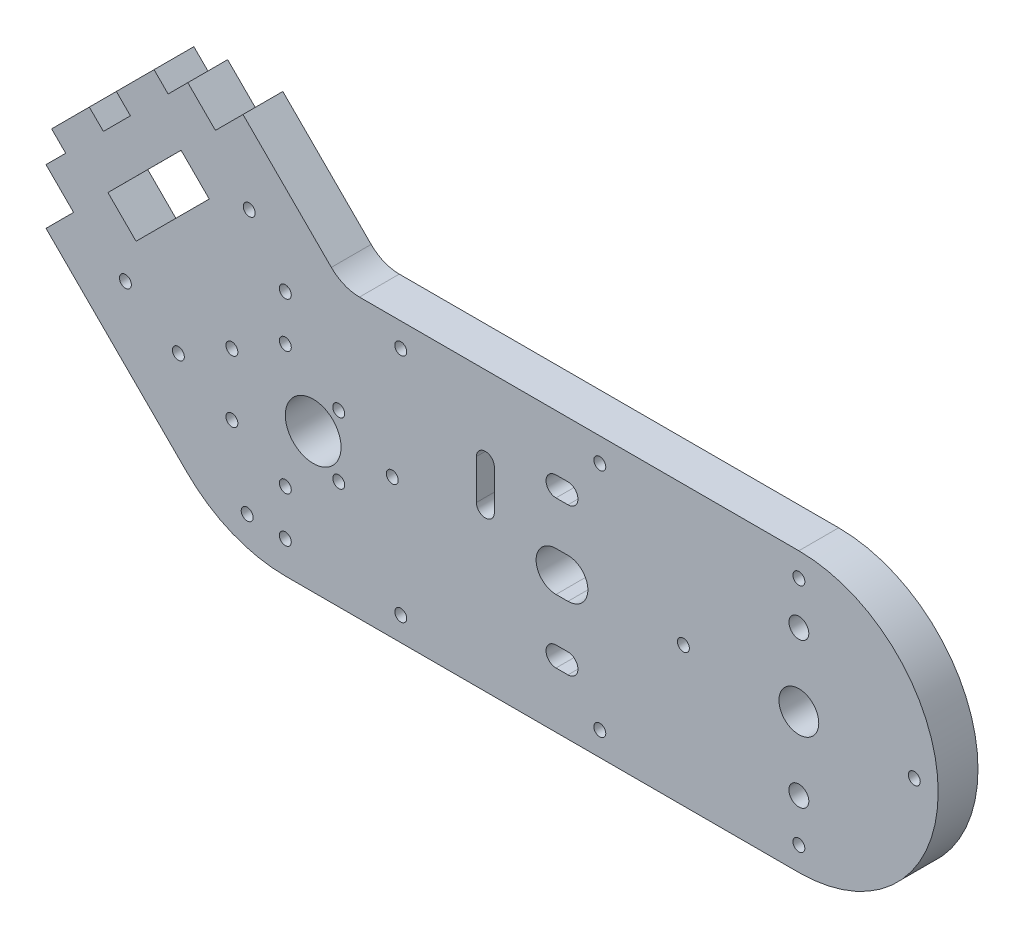
SolidWorks part; units mm, degrees
ref_plane "Front Plane" through (0, 0, 0) normal (0, 0, 1) x (1, 0, 0)
ref_plane "Top Plane" through (0, 0, 0) normal (0, 1, 0) x (1, 0, 0)
ref_plane "Right Plane" through (0, 0, 0) normal (1, 0, 0) x (0, 0, -1)
sketch "Sketch1" plane through (0, 0, 0) normal (0, 0, 1) x (1, 0, 0)
  line L0 (0, -35) -> (-129, -35)
  line L4 (0, 35) -> (-110.37, 35)
  line L9 (-58, 0) -> (-61, 0) construction
  line L10 (-58, -5) -> (-61, -5)
  line L11 (-58, 5) -> (-61, 5)
  line L13 (-58, 18.5) -> (-61, 18.5) construction
  line L14 (-58, 16) -> (-61, 16)
  line L15 (-58, 21) -> (-61, 21)
  line L17 (-58, -18.5) -> (-61, -18.5) construction
  line L18 (-58, -21) -> (-61, -21)
  line L19 (-58, -16) -> (-61, -16)
  line L20 (-78.75, 5) -> (-78.75, 15) construction
  line L21 (-81, 5) -> (-81, 15)
  line L22 (-76.5, 5) -> (-76.5, 15)
  line L25 (0, 0) -> (-129, 0) construction
  line L27 (-189.1079, 10.5847) -> (-182.1808, 17.5169)
  line L28 (-182.1808, 17.5169) -> (-146.5556, 53.168) construction
  line L29 (-146.5556, 53.168) -> (-139.6285, 60.1002)
  line L30 (-146.5556, 53.168) -> (-153.4878, 60.0952)
  line L31 (-182.1808, 17.5169) -> (-189.113, 24.444)
  line L32 (-189.113, 24.444) -> (-184.1651, 29.3955)
  line L33 (-184.1651, 29.3955) -> (-187.7019, 32.9298)
  line L34 (-153.4878, 60.0952) -> (-158.4357, 55.1436)
  line L35 (-158.4357, 55.1436) -> (-161.9726, 58.6778)
  line L36 (-187.7019, 32.9298) -> (-178.2301, 42.4085)
  line L37 (-184.1651, 29.3955) -> (-158.4357, 55.1436) construction
  line L38 (-178.2301, 42.4085) -> (-174.6933, 38.8742)
  line L39 (-161.9726, 58.6778) -> (-171.4443, 49.1992)
  line L40 (-171.4443, 49.1992) -> (-167.9075, 45.6649)
  line L41 (-174.6933, 38.8742) -> (-167.9075, 45.6649)
  line L43 (-189.1079, 10.5847) -> (-153.7397, -24.7578)
  line L44 (-171.3004, 42.2696) -> (-129, 0) construction
  line L45 (-139.6285, 60.1002) -> (-117.4393, 37.9271)
  line L46 (-173.5573, 26.1467) -> (-155.1792, 44.5382)
  line L47 (-155.1792, 44.5382) -> (-148.1081, 37.4671)
  line L48 (-148.1081, 37.4671) -> (-166.4929, 19.0823)
  line L49 (-166.4929, 19.0823) -> (-173.5573, 26.1467)
  line L54 (-129, 0) -> (-138.5766, -26.3114) construction
  line L55 (-129, 26.8701) -> (-129, -26.8701) construction
  line L56 (-155.8701, 0) -> (-102.1299, 0) construction
  line L57 (-129, 0) -> (-129, 15.5) construction
  line L58 (-129, 0) -> (-149.42, 0) construction
  line L59 (-122, 0) -> (-142.42, 0) construction
  line L60 (-142.42, 0) -> (-142.42, -7.7559) construction
  line L61 (-142.42, 7.7559) -> (-142.42, 0) construction
  line L62 (-122, 0) -> (-122, -7.7559) construction
  line L63 (-122, -7.7559) -> (-115.58, -7.7559) construction
  line L64 (-122, 0) -> (-122, 7.7559) construction
  line L65 (-122, 7.7559) -> (-115.58, 7.7559) construction
  line L66 (0, 0) -> (0, 18.25) construction
  circle A0 centre (0, 0) radius 5
  circle A1 centre (29, 0) radius 1.5
  circle A2 centre (0, -18.25) radius 2.5
  circle A3 centre (0, 18.25) radius 2.5
  arc A4 (0, -35) -> (0, 35) centre (0, 0) ccw
  circle A5 centre (0, 29) radius 1.5
  circle A6 centre (0, -29) radius 1.5
  circle A7 centre (-50, -29) radius 1.5
  circle A8 centre (-50, 29) radius 1.5
  circle A9 centre (-100, -29) radius 1.5
  circle A10 centre (-100, 29) radius 1.5
  arc A11 (-58, -5) -> (-58, 5) centre (-58, 0) ccw
  arc A12 (-61, 5) -> (-61, -5) centre (-61, 0) ccw
  arc A13 (-58, 16) -> (-58, 21) centre (-58, 18.5) ccw
  arc A14 (-61, 21) -> (-61, 16) centre (-61, 18.5) ccw
  arc A15 (-58, -21) -> (-58, -16) centre (-58, -18.5) ccw
  arc A16 (-61, -16) -> (-61, -21) centre (-61, -18.5) ccw
  circle A17 centre (-29, 0) radius 1.5
  arc A18 (-81, 5) -> (-76.5, 5) centre (-78.75, 5) ccw
  arc A19 (-76.5, 15) -> (-81, 15) centre (-78.75, 15) ccw
  arc A22 (-129, -35) -> (-153.7397, -24.7578) centre (-129, 0) cw
  arc A23 (-117.4393, 37.9271) -> (-110.37, 35) centre (-110.37, 45) ccw
  circle A27 centre (-169.167, 9.0363) radius 1.5
  circle A28 centre (-138.0656, 40.1604) radius 1.5
  circle A29 centre (-122, 0) radius 7
  circle A30 centre (-129, 26.8701) radius 1.5
  circle A31 centre (-155.8701, 0) radius 1.5
  circle A32 centre (-129, -26.8701) radius 1.5
  circle A33 centre (-102.1299, 0) radius 1.5
  circle A34 centre (-138.5766, -26.3114) radius 1.5
  circle A35 centre (-129, 15.5) radius 1.5
  circle A37 centre (-129, -15.5) radius 1.5
  circle A38 centre (-142.42, 7.7559) radius 1.5
  circle A39 centre (-142.42, -7.7559) radius 1.5
  circle A40 centre (-115.58, -7.7559) radius 1.5
  circle A41 centre (-115.58, 7.7559) radius 1.5
  point P13 (0, -29)
  point P29 (-59.5, 0)
  point P37 (-59.5, 18.5)
  point P45 (-59.5, -18.5)
  point P54 (-78.75, 10)
  point P74 (-102.28, 58.871)
  point P79 (-122, 0)
  point P86 (-164.3682, 35.3424)
  point P91 (-155.9618, 57.6194)
  dimension "D1" = 10
  dimension "D2" = 5
  dimension "D3" = 5
  dimension "D4" = 70
  dimension "D5" = 3
  dimension "D6" = 3
  dimension "D7" = 3
  dimension "D8" = 3
  dimension "D9" = 3
  dimension "D10" = 3
  dimension "D11" = 3
  dimension "D14" = 50
  dimension "D12" = 35
  dimension "D13" = 35
  dimension "D19" = 5
  dimension "D22" = 36.4
  dimension "D35" = 10
  dimension "D33" = 3
  dimension "D37" = 3
  dimension "D36" = 13
  dimension "D39" = 38
  dimension "D41" = 3
  dimension "D42" = 3
  dimension "D43" = 3
  dimension "D44" = 3
  dimension "D46" = 3
  dimension "D47" = 3
  dimension "D48" = 3
  dimension "D49" = 3
  dimension "D50" = 3
  dimension "D51" = 3
  dimension "D52" = 3
  dimension "D15" = 129
  dimension "D16" = 58
  dimension "D17" = 11
  dimension "D18" = 4.5
  dimension "D20" = 10
  dimension "D21" = 110.37
  dimension "D23" = 50.4
  dimension "D24" = 13.4
  dimension "D25" = 9.8
  dimension "D26" = 9.8
  dimension "D27" = 7
  dimension "D28" = 9.8
  dimension "D29" = 9.8
  dimension "D30" = 5
  dimension "D31" = 5
  dimension "D32" = 13.4
  dimension "D34" = 31.3689
  dimension "D38" = 7
  dimension "D40" = 38
  dimension "D45" = 28
  dimension "D53" = 18.25
  dimension "D54" = 18.25
extrude "Boss-Extrude1" add sketch "Sketch1" along normal blind 10
